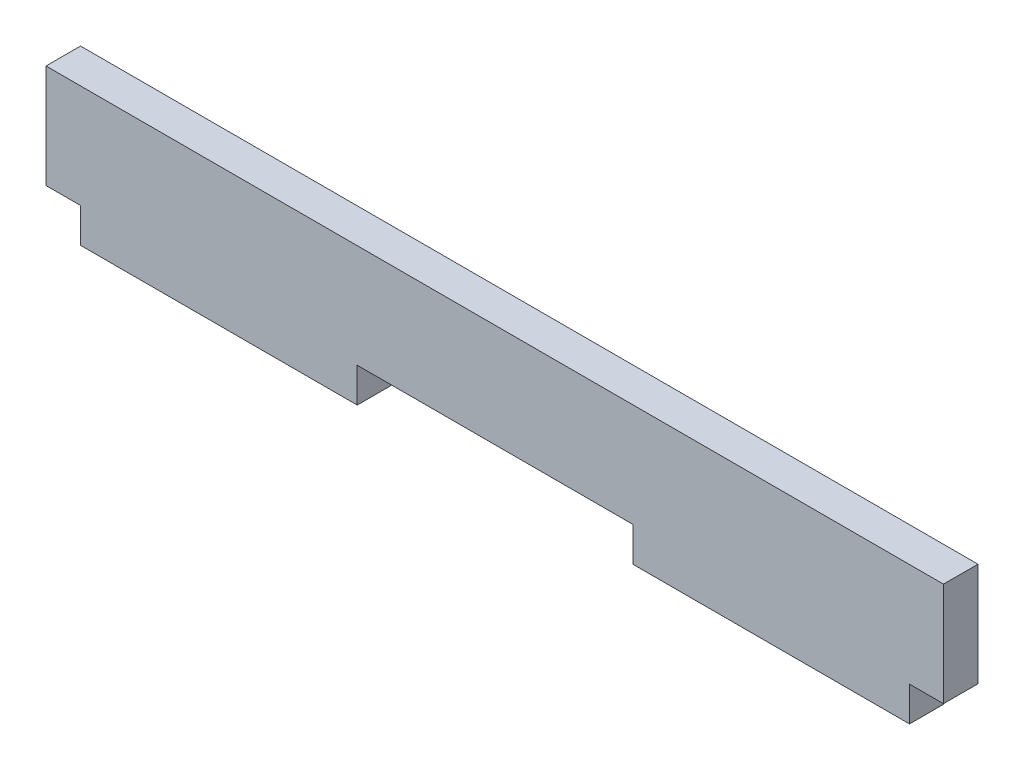
SolidWorks part; units mm, degrees
ref_plane "Front Plane" through (0, 0, 0) normal (0, 0, 1) x (1, 0, 0)
ref_plane "Top Plane" through (0, 0, 0) normal (0, 1, 0) x (1, 0, 0)
ref_plane "Right Plane" through (0, 0, 0) normal (1, 0, 0) x (0, 0, -1)
sketch "Sketch1" plane through (0, 0, 0) normal (0, 0, 1) x (1, 0, 0)
  line L0 (-12.6492, -4.7625) -> (12.7, -4.7625)
  line L1 (-41.275, 4.7625) -> (41.275, 4.7625)
  line L2 (-41.275, 4.7625) -> (-41.275, -4.7625)
  line L3 (-41.275, -4.7625) -> (-38.1, -4.7625)
  line L4 (41.275, 4.7625) -> (41.275, -4.7625)
  line L5 (-41.275, 4.7625) -> (41.275, -4.7625) construction
  line L6 (-41.275, -4.7625) -> (41.275, 4.7625) construction
  line L8 (-12.6492, -4.7625) -> (-12.6492, -7.9375)
  line L9 (-12.6492, -7.9375) -> (-38.1, -7.9375)
  line L10 (-38.1, -4.7625) -> (-38.1, -7.9375)
  line L12 (12.7, -4.7625) -> (12.7, -7.9375)
  line L13 (12.7, -7.9375) -> (38.1508, -7.9375)
  line L14 (38.1508, -4.7625) -> (38.1508, -7.9375)
  line L15 (38.1508, -4.7625) -> (41.275, -4.7625)
  point P0 (0, 0)
  point P14 (25.4254, -7.9375)
  point P15 (-25.3746, -7.9375)
  dimension "D1" = 9.525
  dimension "D2" = 82.55
  dimension "D3" = 3.175
  dimension "D4" = 25.4508
  dimension "D5" = 50.8
  dimension "D6" = 25.4508
  dimension "D7" = 12.7
extrude "Boss-Extrude1" add sketch "Sketch1" along normal mid plane 3.175
